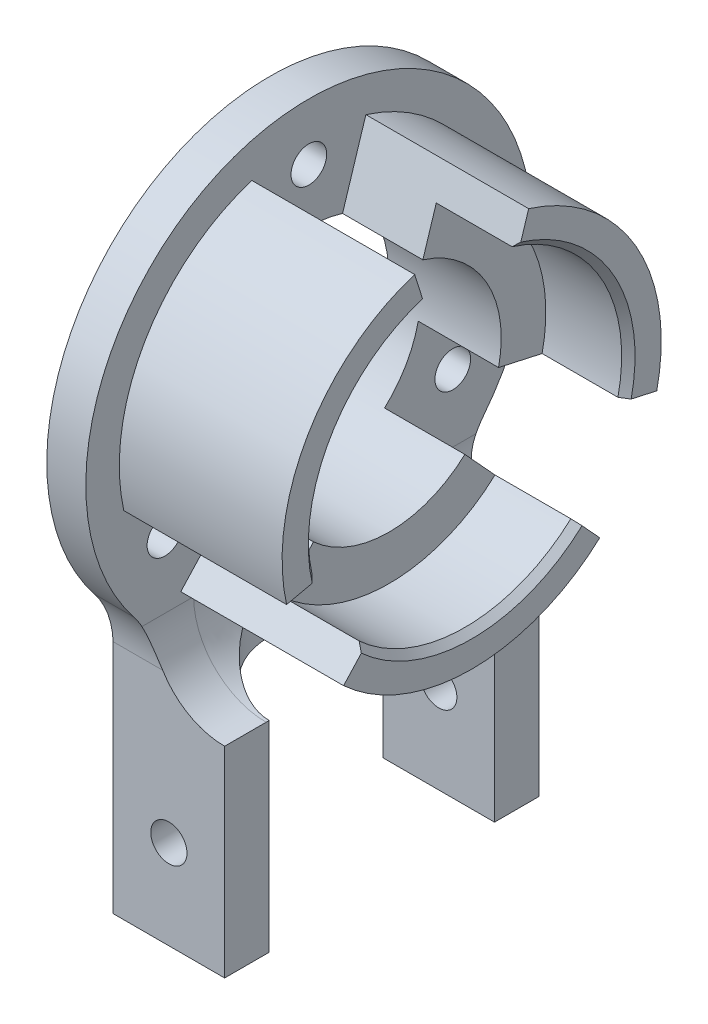
SolidWorks part; units mm, degrees
ref_plane "Front Plane" through (0, 0, 0) normal (0, 0, 1) x (1, 0, 0)
ref_plane "Top Plane" through (0, 0, 0) normal (0, 1, 0) x (1, 0, 0)
ref_plane "Right Plane" through (0, 0, 0) normal (1, 0, 0) x (0, 0, -1)
sketch "Sketch1" plane through (0, 0, 0) normal (1, 0, 0) x (0, 0, -1)
  line L0 (0, 44.2539) -> (0, -44.2539) construction
  line L1 (0, 0) -> (0, 14.9029) construction
  line L2 (0, 0) -> (12.9062, -7.4514) construction
  line L3 (0, 0) -> (-12.9062, -7.4514) construction
  line L4 (55, 0) -> (-55, 0) construction
  line L6 (-14.0532, -20) -> (14.1468, -20)
  line L8 (-14.0532, -20) -> (-14.0532, -16.8806)
  line L9 (14.1468, -20) -> (14.1468, -16.8806)
  circle A0 centre (0, 0) radius 10.05
  circle A2 centre (0, 14.9029) radius 1.6
  circle A3 centre (12.9062, -7.4514) radius 1.6
  circle A4 centre (-12.9062, -7.4514) radius 1.6
  arc A5 (-15.707, -12.381) -> (15.707, -12.381) centre (0, 0) cw
  arc A6 (-15.707, -12.381) -> (-14.0532, -16.8806) centre (-21.7773, -17.1659) cw
  arc A7 (14.1468, -16.8806) -> (15.707, -12.381) centre (21.4154, -16.8806) cw
  dimension "D1" = 20.1
  dimension "D2" = 20
  dimension "D3" = 3.2
  dimension "D6" = 28.2
  dimension "D4" = 120
  dimension "D5" = 120
  dimension "D7" = 20
extrude "Boss-Extrude1" add sketch "Sketch1" along normal blind 3.5
sketch "Sketch2" plane through (3.5, 0, 0) normal (1, 0, 0) x (0, 0, -1)
  line L0 (0, 0) -> (11.3016, 6.525) construction
  line L1 (0, 0) -> (0, -13.05) construction
  line L2 (0, 0) -> (-11.3016, 6.525) construction
  line L3 (3.9242, 12.446) -> (3.0221, 9.5849)
  line L4 (9.8118, -2.1752) -> (12.7407, -2.8245)
  line L5 (8.8165, -9.6215) -> (6.7897, -7.4096)
  line L6 (-8.8165, -9.6215) -> (-6.7897, -7.4096)
  line L7 (-9.8118, -2.1752) -> (-12.7407, -2.8245)
  line L8 (-3.9242, 12.446) -> (-3.0221, 9.5849)
  arc A1 (3.0221, 9.5849) -> (9.8118, -2.1752) centre (0, 0) cw
  circle A2 centre (0, 0) radius 10.05 construction
  arc A3 (6.7897, -7.4096) -> (-6.7897, -7.4096) centre (0, 0) cw
  arc A4 (-3.0221, 9.5849) -> (-9.8118, -2.1752) centre (0, 0) ccw
  arc A5 (3.9242, 12.446) -> (12.7407, -2.8245) centre (0, 0) cw
  arc A6 (-8.8165, -9.6215) -> (8.8165, -9.6215) centre (0, 0) ccw
  arc A7 (-12.7407, -2.8245) -> (-3.9242, 12.446) centre (0, 0) cw
  point P17 (8.7036, 5.025)
  point P20 (0, -10.05)
  point P21 (-8.7036, 5.025)
  dimension "D1" = 120
  dimension "D2" = 120
  dimension "D3" = 85
  dimension "D4" = 85
  dimension "D5" = 85
  dimension "D6" = 85
  dimension "D7" = 85
  dimension "D8" = 85
  dimension "D9" = 3
extrude "Boss-Extrude2" add sketch "Sketch2" along normal blind 5.8
sketch "Sketch3" plane through (9.3, 0, 0) normal (1, 0, 0) x (0, 0, -1)
  line L0 (9.8118, -2.1752) -> (12.7407, -2.8245) construction
  line L1 (-12.7407, -2.8245) -> (-9.8118, -2.1752) construction
  line L2 (8.8165, -9.6215) -> (6.7897, -7.4096) construction
  line L3 (6.7897, -7.4096) -> (11.485, -12.5337)
  line L4 (-6.7897, -7.4096) -> (-11.485, -12.5337)
  line L5 (-9.8118, -2.1752) -> (-16.597, -3.6795)
  line L6 (-3.0221, 9.5849) -> (-5.112, 16.2132)
  line L7 (3.0221, 9.5849) -> (5.112, 16.2132)
  line L8 (9.8118, -2.1752) -> (16.597, -3.6795)
  arc A0 (3.0221, 9.5849) -> (9.8118, -2.1752) centre (0, 0) cw
  arc A1 (5.112, 16.2132) -> (16.597, -3.6795) centre (0, 0) cw
  arc A2 (11.485, -12.5337) -> (-11.485, -12.5337) centre (0, 0) cw
  arc A3 (-16.597, -3.6795) -> (-5.112, 16.2132) centre (0, 0) cw
  arc A4 (-3.0221, 9.5849) -> (-9.8118, -2.1752) centre (0, 0) ccw
  arc A5 (-6.7897, -7.4096) -> (6.7897, -7.4096) centre (0, 0) ccw
  dimension "D1" = 17
extrude "Boss-Extrude3" add sketch "Sketch3" along normal blind 7.2 from surface starting at face at (3.5, -7.4514, 11.3062)
sketch "Sketch4" plane through (10.7, 0, 0) normal (1, 0, 0) x (0, 0, -1)
  line L0 (9.8118, -2.1752) -> (16.597, -3.6795) construction
  line L1 (-6.7897, -7.4096) -> (-11.485, -12.5337) construction
  line L2 (-16.597, -3.6795) -> (-9.8118, -2.1752) construction
  line L3 (-3.0221, 9.5849) -> (-5.112, 16.2132) construction
  line L4 (5.112, 16.2132) -> (3.0221, 9.5849) construction
  line L5 (11.485, -12.5337) -> (6.7897, -7.4096) construction
  line L6 (-13.717, -3.041) -> (-16.597, -3.6795)
  line L7 (-4.2249, 13.3997) -> (-5.112, 16.2132)
  line L8 (4.2249, 13.3997) -> (5.112, 16.2132)
  line L9 (13.717, -3.041) -> (16.597, -3.6795)
  line L10 (9.492, -10.3587) -> (11.485, -12.5337)
  line L11 (-9.492, -10.3587) -> (-11.485, -12.5337)
  arc A0 (5.112, 16.2132) -> (16.597, -3.6795) centre (0, 0) cw
  arc A1 (11.485, -12.5337) -> (-11.485, -12.5337) centre (0, 0) cw
  arc A2 (-16.597, -3.6795) -> (-5.112, 16.2132) centre (0, 0) cw
  arc A3 (-5.112, 16.2132) -> (-16.597, -3.6795) centre (0, 0) ccw construction
  arc A4 (-13.717, -3.041) -> (-4.2249, 13.3997) centre (0, 0) cw
  arc A5 (4.2249, 13.3997) -> (13.717, -3.041) centre (0, 0) cw
  arc A6 (9.492, -10.3587) -> (-9.492, -10.3587) centre (0, 0) cw
  dimension "D1" = 14.05
extrude "Boss-Extrude4" add sketch "Sketch4" along normal blind 7.4
sketch "Sketch5" plane through (3.5, 0, 0) normal (1, 0, 0) x (0, 0, -1)
  line L0 (-14.0532, -20) -> (14.1468, -20) construction
  line L1 (-14.0532, -38) -> (-10.0532, -38)
  line L2 (-14.0532, -38) -> (-14.0532, -20)
  line L3 (-14.0532, -20) -> (-10.0532, -20)
  line L4 (-10.0532, -38) -> (-10.0532, -20)
  line L5 (-14.0532, -38) -> (-10.0532, -20) construction
  line L6 (-14.0532, -20) -> (-10.0532, -38) construction
  line L8 (10.1468, -38) -> (14.1468, -38)
  line L9 (10.1468, -38) -> (10.1468, -20)
  line L10 (10.1468, -20) -> (14.1468, -20)
  line L11 (14.1468, -38) -> (14.1468, -20)
  line L12 (10.1468, -38) -> (14.1468, -20) construction
  line L13 (10.1468, -20) -> (14.1468, -38) construction
  line L14 (-14.0532, -16.8806) -> (-14.0532, -20) construction
  point P0 (-12.0532, -29)
  point P7 (12.1468, -29)
  dimension "D1" = 20.2
  dimension "D3" = 18
  dimension "D4" = 4
extrude "Boss-Extrude5" add sketch "Sketch5" along normal blind 10 from surface starting at face at (0, -7.4514, -14.5062)
sketch "Sketch7" plane through (0, 0, -10.1468) normal (0, 0, 1) x (1, 0, 0)
  line L0 (0, -44.7868) -> (0, 44.7868) construction
  line L1 (0, -30) -> (10, -30) construction
  line L2 (10, -38) -> (10, -20) construction
  line L3 (3.5, -20) -> (0, -20) construction
  circle A0 centre (5, -30) radius 1.625
  point P8 (5, -30)
  dimension "D1" = 3.25
  dimension "D2" = 10
extrude "Cut-Extrude1" cut sketch "Sketch7" against normal through all both and the other way through all
fillet "Fillet2" radius 6.5 2 edges at (3.5, -20, -12.1468) (3.5, -20, 12.0532)
fillet "Fillet3" radius 6.5 2 edges at (3.5, -16.8199, -10.1468) (3.5, -16.8544, 10.0532)
chamfer "Chamfer3" distance 0.6 angle 45 4 edges at (0, 0, -10.05) (18.1, -14.05, 0) (18.1, 7.025, -12.1677) (18.1, 7.025, 12.1677)
